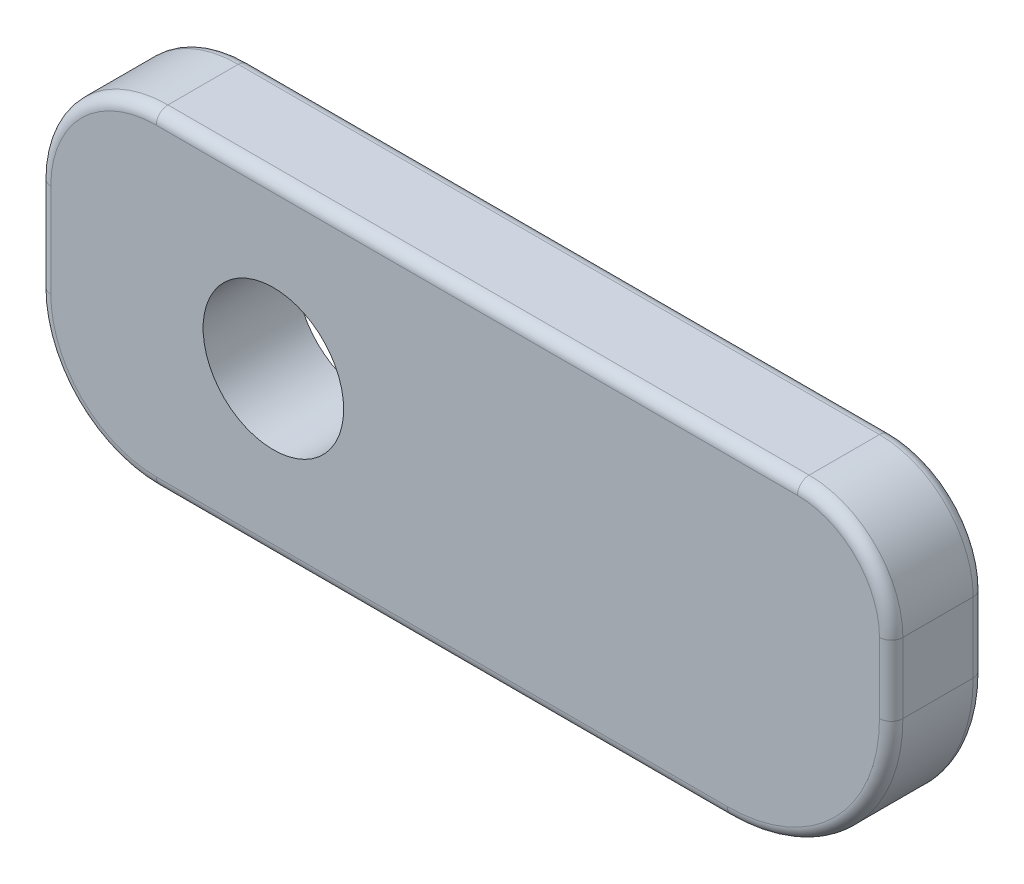
SolidWorks part; units mm, degrees
material "Nickel"
ref_plane "Front Plane" through (0, 0, 0) normal (0, 0, 1) x (1, 0, 0)
ref_plane "Top Plane" through (0, 0, 0) normal (0, 1, 0) x (1, 0, 0)
ref_plane "Right Plane" through (0, 0, 0) normal (1, 0, 0) x (0, 0, -1)
sketch "Sketch1" plane through (0, 0, 0) normal (0, 0, 1) x (1, 0, 0)
  line L0 (0, 0) -> (0, 35.56)
  line L1 (0, 35.56) -> (92.3798, 35.56)
  line L2 (92.3798, 35.56) -> (92.3798, 0)
  line L3 (92.3798, 0) -> (0, 0)
  line L4 (0, 17.78) -> (92.3798, 17.78) construction
  circle A0 centre (25.4, 17.78) radius 7.62
  dimension "D3" = 25.4
  dimension "D4" = 15.24
  dimension "D1" = 35.56
  dimension "D2" = 92.3798
extrude "Boss-Extrude1" add sketch "Sketch1" along normal blind 10.16
fillet "Fillet1" radius 1.27 4 edges at (0, 17.78, 10.16) (46.1899, 0, 10.16) (92.3798, 17.78, 10.16) (46.1899, 35.56, 10.16)
fillet "Fillet2" radius 1.27 4 edges at (92.3798, 17.78, 0) (46.1899, 0, 0) (46.1899, 35.56, 0) (0, 17.78, 0)
fillet "Fillet3" radius 17.78 3 edges at (92.0078, 0.372, 9.788) (92.0078, 0.372, 0.372) (92.3798, 0, 5.08)
fillet "Fillet4" radius 10.16 3 edges at (92.0078, 35.188, 9.788) (92.0078, 35.188, 0.372) (92.3798, 35.56, 5.08)
fillet "Fillet5" radius 12.7 3 edges at (0.372, 35.188, 0.372) (0.372, 35.188, 9.788) (0, 35.56, 5.08)
fillet "Fillet6" radius 12.7 3 edges at (0.372, 0.372, 0.372) (0.372, 0.372, 9.788) (0, 0, 5.08)
